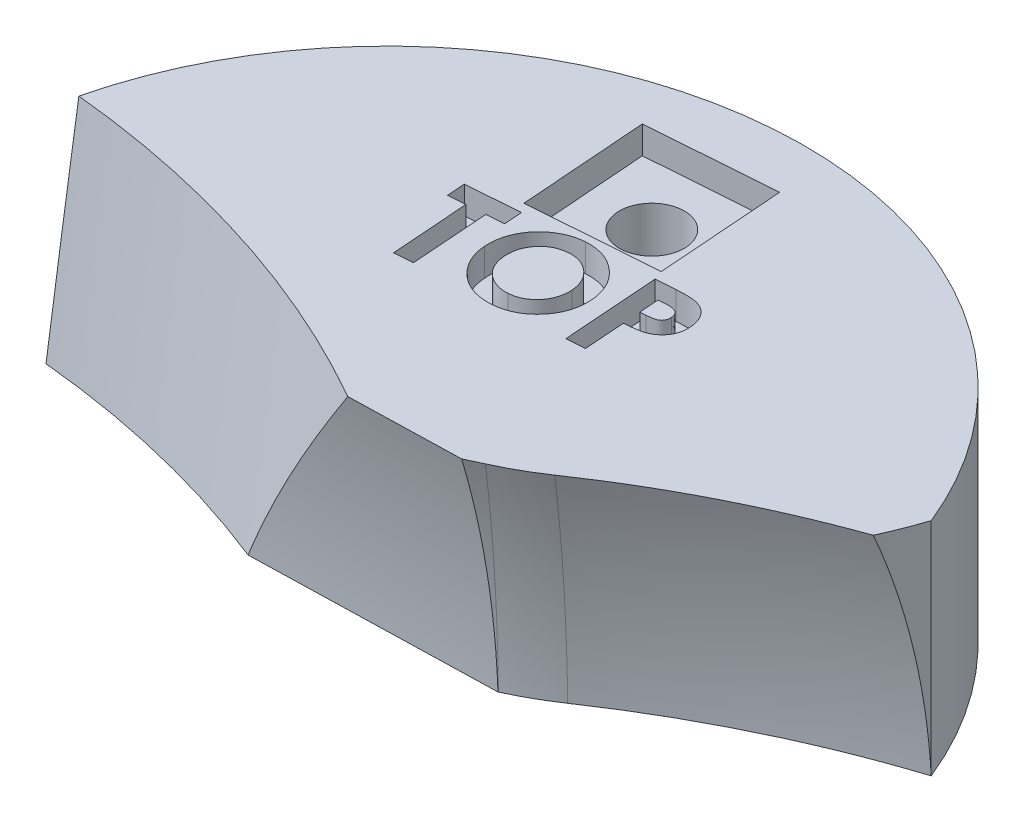
SolidWorks part; units mm, degrees
ref_plane "Front Plane" through (0, 0, 0) normal (0, 0, 1) x (1, 0, 0)
ref_plane "Top Plane" through (0, 0, 0) normal (0, 1, 0) x (1, 0, 0)
ref_plane "Right Plane" through (0, 0, 0) normal (1, 0, 0) x (0, 0, -1)
sketch "Sketch1" plane through (0, 0, 0) normal (0, 1, 0) x (1, 0, 0)
  circle A0 centre (0, 0) radius 16
  dimension "D1" = 32
extrude "Boss-Extrude1" add sketch "Sketch1" along normal blind 8 contours A0
sketch "Sketch2" plane through (0, 8, 0) normal (0, 1, 0) x (1, 0, 0)
  circle A0 centre (0, 0) radius 2.32
  dimension "D1" = 4.64
extrude "Cut-Extrude1" cut sketch "Sketch2" against normal blind 1
sketch "Sketch3" plane through (0, 7, 0) normal (0, 1, 0) x (1, 0, 0)
  circle A0 centre (0, 0) radius 1.175
  dimension "D1" = 2.35
extrude "Cut-Extrude2" cut sketch "Sketch3" against normal through all
sketch "Sketch5" plane through (0, 0, 0) normal (0, -1, 0) x (1, 0, 0)
  circle A0 centre (0, 0) radius 2.3
  dimension "D1" = 4.6
extrude "Cut-Extrude3" cut sketch "Sketch5" against normal blind 2
ref_point "Point1"
ref_plane "Plane1" through (0, -1.3, 0) normal (0, 1, 0) x (1, 0, 0)
sketch "Sketch7" plane through (0, -1.3, 0) normal (0, 1, 0) x (1, 0, 0)
  line L0 (25.8416, -3.3693) -> (25.8416, -73.1493)
  circle A2 centre (25.8416, -38.2593) radius 34.89
  circle A3 centre (25.8416, -38.2593) radius 34.89
  point P2 (19.4807, -7.9991)
  dimension "D1" = 0.6
revolve "Cut-Revolve1" cut sketch "Sketch7" angle 360 about L0 region at (11.0338, -1.3, 38.2593)
sketch "Sketch16" plane through (0, -1.3, 0) normal (0, 1, 0) x (1, 0, 0)
  line L0 (25.8416, -38.2593) -> (0, 0) construction
  line L1 (6.313, -9.3466) -> (16.6251, -4.6087) construction
  line L2 (6.313, -9.3466) -> (15.7172, -2.9947) construction
  line L3 (0, 0) -> (19.2737, -41.9535) construction
  line L4 (19.2737, -41.9535) -> (25.8416, -38.2593)
  line L5 (13.1693, -76.3053) -> (25.378, -7.6016)
  circle A1 centre (0, 0) radius 11.2789
  circle A2 centre (25.8416, -38.2593) radius 34.89
  circle A3 centre (25.8416, -38.2593) radius 34.89
  arc A4 (14.5887, -6.5703) -> (0.6472, -15.9869) centre (0, 0) ccw construction
  circle A5 centre (19.2737, -41.9535) radius 34.89
  point P16 (0, 0)
  dimension "D2" = 22.5578
  dimension "D3" = 9.36
  dimension "D4" = 9.362
  dimension "D1" = 0.6
revolve "Cut-Revolve10" cut sketch "Sketch16" angle 360 about L5 region at (7.7834, -1.3, 36.036) region at (12.9143, -1.3, 73.5811)
revolve "Cut-Revolve12" cut sketch "Sketch16<4>" angle 360 about L4 region at (5.5347, -1.3, 9.8405)
sketch "Sketch16<4>" plane through (0, -1.3, 0) normal (0, 1, 0) x (1, 0, 0) same geometry as "Sketch16"
sketch "Sketch17" plane through (0, -1.3, 0) normal (0, 1, 0) x (1, 0, 0)
  line L0 (-17.0634, -42.9) -> (0, 0) construction
  line L1 (0, 0) -> (19.2737, -41.9535) construction
  circle A0 centre (-17.0634, -42.9) radius 34.89
  arc A1 (5.3294, -11.3531) -> (-1.9621, -15.8792) centre (19.2737, -41.9535) ccw construction
  arc A2 (5.3294, -11.3531) -> (-1.9621, -15.8792) centre (19.2737, -41.9535) ccw
  circle A3 centre (19.2737, -41.9535) radius 34.89 construction
  point P5 (1.5387, -13.3826)
  point P10 (-16.7976, -43.0016)
  dimension "D1" = 46.364
extrude "Cut-Extrude6" cut sketch "Sketch17" along normal through all contours A0 region at (-17.0634, -1.3, 42.9)
sketch "Sketch18" plane through (0, -1.3, 0) normal (0, 1, 0) x (1, 0, 0)
  line L0 (-4.1685, -10.4803) -> (4.7085, -10.2491)
  line L1 (0, 0) -> (19.2737, -41.9535) construction
  line L2 (-17.0634, -42.9) -> (0, 0) construction
  line L3 (-17.0634, -42.9) -> (19.2737, -41.9535)
  line L4 (19.2737, -41.9535) -> (4.7085, -10.2491)
  line L5 (-4.1685, -10.4803) -> (-17.0634, -42.9)
  circle A2 centre (19.2737, -41.9535) radius 34.89 construction
  circle A3 centre (-17.0634, -42.9) radius 34.89 construction
revolve "Cut-Revolve13" cut sketch "Sketch18" angle 360 about L3
sketch "Sketch19" plane through (0, 8, 0) normal (0, 1, 0) x (1, 0, 0)
  line L0 (-0.2473, 2.3068) -> (-0.4617, 4.3068)
  line L1 (0, 0) -> (-0.2473, 2.3068) construction
  line L2 (0, 0) -> (1.1511, -10.7367) construction
  arc A0 (15.1773, -5.0646) -> (-13.7587, -8.1668) centre (0, 0) ccw construction
  arc A1 (15.1773, -5.0646) -> (-13.7587, -8.1668) centre (0, 0) ccw
  arc A2 (-13.7587, -8.1668) -> (15.1773, -5.0646) centre (1.1511, -10.7367) cw
  circle A3 centre (0, 0) radius 2.32 construction
  arc M7 (14.5887, -6.5703) -> (-13.7587, -8.1668) centre (0, 0) ccw
  dimension "D1" = 2
extrude "Cut-Extrude7" cut sketch "Sketch19" against normal through all contours A2 M7 region at (-0.7275, 8, -6.7858)
chamfer "Chamfer1" distance 1 distance2 8 1 edges at (-7.3502, 8, 9.3893) first distance on face at (0, 8, 2.32)
sketch "Sketch20" plane through (0, 8, 0) normal (0, 1, 0) x (1, 0, 0)
  line L0 (15.1773, -5.0646) -> (-13.555, -7.1819) construction
  text T0 "<b>TOP</b>"
extrude "Cut-Extrude8" cut sketch "Sketch20" against normal blind 1
sketch "Sketch21" plane through (0, 8, 0) normal (0, 1, 0) x (1, 0, 0)
  line L0 (-2.2751, -6.3508) -> (-2.9468, -6.4006) construction
  line L1 (-2.1422, -2.4851) -> (2.4851, -2.1422)
  line L2 (-2.1422, -2.4851) -> (-2.4851, 2.1422)
  line L3 (-2.4851, 2.1422) -> (2.1422, 2.4851)
  line L4 (2.4851, -2.1422) -> (2.1422, 2.4851)
  line L5 (-2.1422, -2.4851) -> (2.1422, 2.4851) construction
  line L6 (-2.4851, 2.1422) -> (2.4851, -2.1422) construction
  circle A0 centre (0, 0) radius 2.32 construction
  point P0 (0, 0)
  circle M9 centre (0, 0) radius 2.32
extrude "Cut-Extrude10" cut sketch "Sketch21" against normal up to surface (1 mm away) contours L3 L2 M9 | L4 L3 M9 | L1 L4 M9 | L2 L1 M9 region at (-1.6637, 8, 1.93) region at (1.93, 8, 1.6637) region at (-1.93, 8, -1.6637) region at (1.6637, 8, -1.93) up to face at (0, 7, 1.175)
